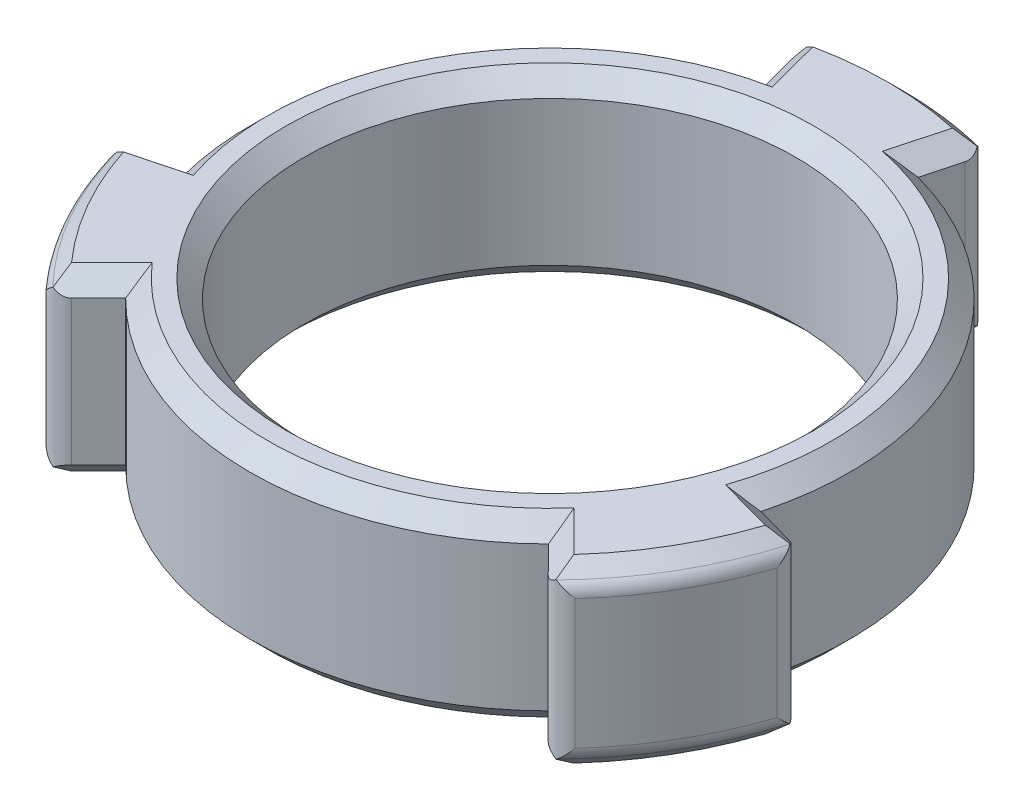
SolidWorks part; units mm, degrees
material "ABS"
ref_plane "Front Plane" through (0, 0, 0) normal (0, 0, 1) x (1, 0, 0)
ref_plane "Top Plane" through (0, 0, 0) normal (0, 1, 0) x (1, 0, 0)
ref_plane "Right Plane" through (0, 0, 0) normal (1, 0, 0) x (0, 0, -1)
sketch "Çizim1" plane through (0, 0, 0) normal (0, 1, 0) x (1, 0, 0)
  circle A0 centre (0, 0) radius 13.6
  circle A1 centre (0, 0) radius 19.75
  dimension "D1" = 27.2
  dimension "D2" = 39.5
extrude "Yükseklik-Ekstrüzyon1" add sketch "Çizim1" along normal blind 10
sketch "Çizim7" plane through (0, 10, 0) normal (0, 1, 0) x (1, 0, 0)
  line L0 (-11.7795, -11.6963) -> (-26.8526, -26.6631)
  line L1 (11.6963, -11.7795) -> (23.5897, -23.7574)
  line L2 (23.5897, -23.7574) -> (-26.8526, -26.6631)
  arc A0 (11.6963, -11.7795) -> (-11.7795, -11.6963) centre (0, 0) cw
  circle A1 centre (0, 0) radius 13.6 construction
  dimension "D1" = 3
extrude "Kes-Ekstrüzyon1" cut sketch "Çizim7" against normal through all
pattern_circular "Dairesel Kaplama1" count 3 over 360 about axis through (0, 10, 0) along (0, -1, 0) of "Kes-Ekstrüzyon1" reverse direction yes
chamfer "Pah1" distance 1 angle 45 26 edges at (0, 10, 13.6) (14.4053, 10, -8.249) (17.5389, 10, 4.7662) (17.0689, 10, 9.9355) (12.8061, 10, 12.8971) (-0.0588, 10, 16.5999) (-12.8971, 10, 12.8061) (-17.1389, 10, 9.8144) (-17.5723, 10, 4.6418) (-14.3465, 10, -8.3509) (-4.6418, 10, -17.5723) (0.07, 10, -19.7499) (4.7662, 10, -17.5389) (0, 0, 13.6) (-4.6418, 0, -17.5723) (-14.3465, 0, -8.3509) (-17.5723, 0, 4.6418) (-17.1389, 0, 9.8144) (-12.8971, 0, 12.8061) (-0.0588, 0, 16.5999) (12.8061, 0, 12.8971) (17.0689, 0, 9.9355) (17.5389, 0, 4.7662) (14.4053, 0, -8.249) (4.7662, 0, -17.5389) (0.07, 0, -19.7499)
fillet "Radyus1" radius 1 12 edges at (0.07, 1, -19.7499) (5.1792, 5, -19.0588) (0.07, 9, -19.7499) (-5.0441, 5, -19.095) (17.0689, 1, 9.9355) (13.9158, 5, 14.0147) (17.0689, 9, 9.9355) (19.0588, 5, 5.1792) (-17.1389, 1, 9.8144) (-19.095, 5, 5.0441) (-17.1389, 9, 9.8144) (-14.0147, 5, 13.9158)
